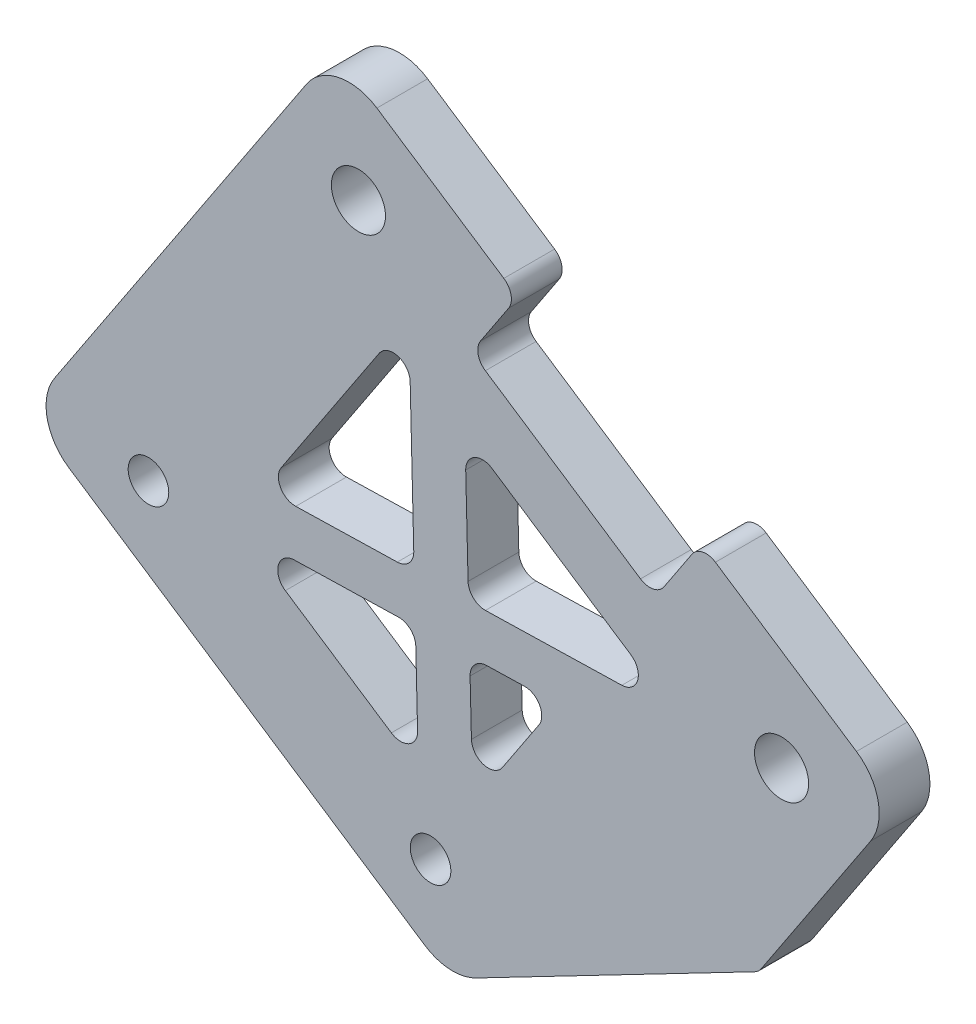
SolidWorks part; units mm, degrees
ref_plane "前视基准面" through (0, 0, 0) normal (0, 0, 1) x (1, 0, 0)
ref_plane "上视基准面" through (0, 0, 0) normal (0, 1, 0) x (1, 0, 0)
ref_plane "右视基准面" through (0, 0, 0) normal (1, 0, 0) x (0, 0, -1)
other "Configuration Table"
sketch "草图1" plane through (0, 0, 0) normal (0, 0, 1) x (1, 0, 0)
  line L0 (3.6524, -4.5189) -> (1.4155, -4.5744)
  line L1 (2.3538, -9.3298) -> (4.5111, -6.0705)
  line L2 (0.4407, -5.5989) -> (0.5202, -8.8027)
  line L3 (0.7984, -20.8838) -> (17.2757, -12.3263)
  line L4 (17.6486, -11.9908) -> (24.1289, -2.2002)
  line L5 (23.283, 1.9573) -> (14.9442, 7.4766)
  line L6 (13.5583, 7.1947) -> (11.9025, 4.693)
  line L7 (10.5167, 4.4111) -> (1.344, 10.4824)
  line L8 (1.062, 11.8682) -> (2.7178, 14.3699)
  line L9 (2.4359, 15.7557) -> (-5.0691, 20.7231)
  line L10 (-9.2266, 19.8773) -> (-24.1289, -2.6376)
  line L11 (-23.283, -6.7951) -> (-2.2401, -20.7231)
  line L12 (-3.794, -4.7038) -> (-9.955, -4.8568)
  line L13 (-2.6627, -9.9802) -> (-2.7695, -5.6787)
  line L14 (-10.4821, -6.6904) -> (-4.2143, -10.839)
  line L15 (1.3464, -1.7892) -> (9.4133, -1.5888)
  line L16 (0.182, 4.818) -> (0.3218, -0.8143)
  line L17 (9.9404, 0.2448) -> (1.7336, 5.6768)
  line L18 (-9.8676, -2.0677) -> (-3.8632, -1.9185)
  line L19 (-4.9355, 8.2329) -> (-10.7263, -0.516)
  line L20 (-2.8884, -0.894) -> (-3.1019, 7.7057)
  arc A0 (17.5213, -0.2252) -> (20.1898, -1.9914) centre (18.8556, -1.1083) ccw
  arc A1 (20.1898, -1.9914) -> (17.5213, -0.2252) centre (18.8556, -1.1083) ccw
  arc A2 (17.2757, -12.3263) -> (17.6486, -11.9908) centre (16.8148, -11.4388) ccw
  arc A3 (24.1289, -2.2002) -> (23.283, 1.9573) centre (21.6272, -0.5444) ccw
  arc A4 (14.9442, 7.4766) -> (13.5583, 7.1947) centre (14.3922, 6.6427) ccw
  arc A5 (10.5167, 4.4111) -> (11.9025, 4.693) centre (11.0686, 5.245) ccw
  arc A6 (1.062, 11.8682) -> (1.344, 10.4824) centre (1.8959, 11.3163) ccw
  arc A7 (2.7178, 14.3699) -> (2.4359, 15.7557) centre (1.8839, 14.9218) ccw
  arc A8 (-5.0691, 20.7231) -> (-9.2266, 19.8773) centre (-6.7249, 18.2215) ccw
  arc A9 (-24.1289, -2.6376) -> (-23.283, -6.7951) centre (-21.6272, -4.2935) ccw
  arc A10 (-2.2401, -20.7231) -> (0.7984, -20.8838) centre (-0.5843, -18.2215) ccw
  arc A11 (4.5111, -6.0705) -> (3.6524, -4.5189) centre (3.6773, -5.5185) ccw
  arc A12 (0.5202, -8.8027) -> (2.3538, -9.3298) centre (1.5199, -8.7779) ccw
  arc A13 (0.6065, -5.0222) -> (0.4407, -5.5989) centre (1.4404, -5.5741) ccw
  arc A14 (1.4155, -4.5744) -> (0.6065, -5.0222) centre (1.4404, -5.5741) ccw
  arc A15 (-2.7695, -5.6787) -> (-3.794, -4.7038) centre (-3.7692, -5.7035) ccw
  arc A16 (-4.2143, -10.839) -> (-2.6627, -9.9802) centre (-3.6624, -10.0051) ccw
  arc A17 (-10.7641, -5.3046) -> (-10.4821, -6.6904) centre (-9.9302, -5.8565) ccw
  arc A18 (-9.955, -4.8568) -> (-10.7641, -5.3046) centre (-9.9302, -5.8565) ccw
  arc A19 (-3.6471, -14.995) -> (-0.1447, -17.3132) centre (-1.8959, -16.1541) ccw
  arc A20 (-0.1447, -17.3132) -> (-3.6471, -14.995) centre (-1.8959, -16.1541) ccw
  arc A21 (-20.3248, -3.9563) -> (-16.8225, -6.2744) centre (-18.5736, -5.1154) ccw
  arc A22 (-16.8225, -6.2744) -> (-20.3248, -3.9563) centre (-18.5736, -5.1154) ccw
  arc A23 (0.3218, -0.8143) -> (1.3464, -1.7892) centre (1.3215, -0.7895) ccw
  arc A24 (0.3478, 5.3948) -> (0.182, 4.818) centre (1.1817, 4.8429) ccw
  arc A25 (1.7336, 5.6768) -> (0.3478, 5.3948) centre (1.1817, 4.8429) ccw
  arc A26 (9.4133, -1.5888) -> (9.9404, 0.2448) centre (9.3885, -0.5891) ccw
  arc A27 (-10.7263, -0.516) -> (-9.8676, -2.0677) centre (-9.8924, -1.068) ccw
  arc A28 (-3.1019, 7.7057) -> (-4.9355, 8.2329) centre (-4.1016, 7.6809) ccw
  arc A29 (-3.8632, -1.9185) -> (-2.8884, -0.894) centre (-3.8881, -0.9189) ccw
  arc A30 (-7.4952, 16.3329) -> (-4.8268, 14.5667) centre (-6.161, 15.4498) ccw
  arc A31 (-4.8268, 14.5667) -> (-7.4952, 16.3329) centre (-6.161, 15.4498) ccw
extrude "凸台-拉伸1" add sketch "草图1" along normal blind 3
sketch "草图2" plane through (0, 0, 0) normal (0, 0, -1) x (-1, 0, 0)
  circle A0 centre (1.8959, -16.1541) radius 2.1
  circle A1 centre (18.5736, -5.1154) radius 2.1
  circle A2 centre (18.5736, -5.1154) radius 1.2
  circle A3 centre (1.8959, -16.1541) radius 1.2
  dimension "D1" = 2.4
  dimension "D2" = 2.4
extrude "凸台-拉伸2" add sketch "草图2" against normal up to surface (3 mm away) up to face at (-5.908, 1.7921, 3)
